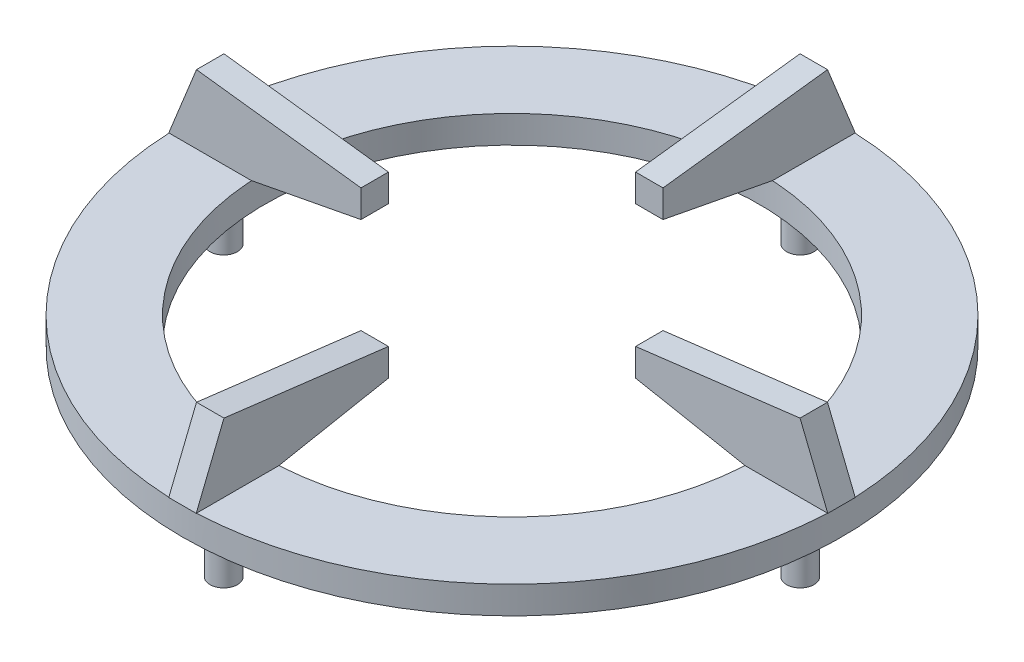
SolidWorks part; units mm, degrees
material "AISI 1010 Steel, hot rolled bar"
ref_plane "Front Plane" through (0, 0, 0) normal (0, 0, 1) x (1, 0, 0)
ref_plane "Top Plane" through (0, 0, 0) normal (0, 1, 0) x (1, 0, 0)
ref_plane "Right Plane" through (0, 0, 0) normal (1, 0, 0) x (0, 0, -1)
sketch "Sketch1" plane through (0, 0, 0) normal (0, 1, 0) x (1, 0, 0)
  circle A0 centre (0, 0) radius 18
  circle A1 centre (0, 0) radius 24
  dimension "D1" = 36
  dimension "D2" = 48
extrude "Boss-Extrude1" add sketch "Sketch1" along normal blind 2
sketch "Sketch3" plane through (0, 0, 0) normal (0, 0, 1) x (1, 0, 0)
  line L0 (24, 2) -> (21.9799, 7)
  line L1 (21.9799, 7) -> (10, 5.5291)
  line L2 (10, 5.5291) -> (10, 3.5291)
  line L3 (10, 3.5291) -> (18, 2)
  line L4 (0, 12.8691) -> (0, -11.8083) construction
  line L5 (24, 2) -> (-24, 2) construction
  line L6 (18, 2) -> (24, 2)
  line L7 (-10, 3.5291) -> (-18, 2)
  line L8 (-10, 5.5291) -> (-10, 3.5291)
  line L9 (-21.9799, 7) -> (-10, 5.5291)
  line L10 (-24, 2) -> (-21.9799, 7)
  line L11 (-18, 2) -> (-24, 2)
  dimension "D1" = 5
  dimension "D2" = 68
  dimension "D3" = 8
  dimension "D4" = 2
  dimension "D5" = 105
extrude "Boss-Extrude2" add sketch "Sketch3" along normal blind 1 and the other way blind 1
sketch "Sketch4" plane through (0, 0, 0) normal (1, 0, 0) x (0, 0, -1)
  line L0 (24, 2) -> (21.9799, 7)
  line L1 (21.9799, 7) -> (10, 5.5291)
  line L2 (10, 5.5291) -> (10, 3.5291)
  line L3 (10, 3.5291) -> (18, 2)
  line L4 (24, 2) -> (1, 2) construction
  line L5 (0, -8.6387) -> (0, 12.4069) construction
  line L6 (18, 2) -> (24, 2)
  line L7 (-10, 3.5291) -> (-18, 2)
  line L8 (-10, 5.5291) -> (-10, 3.5291)
  line L9 (-21.9799, 7) -> (-10, 5.5291)
  line L10 (-24, 2) -> (-21.9799, 7)
  line L11 (-18, 2) -> (-24, 2)
  dimension "D1" = 5
  dimension "D2" = 8
  dimension "D3" = 2
  dimension "D4" = 68
  dimension "D5" = 105
extrude "Boss-Extrude3" add sketch "Sketch4" along normal blind 1 and the other way blind 1
sketch "Sketch5" plane through (0, 0, 0) normal (0, -1, 0) x (1, 0, 0)
  circle A0 centre (0, 0) radius 21
  circle A1 centre (21, 0) radius 1
  circle A2 centre (0, 21) radius 1
  circle A3 centre (-21, 0) radius 1
  circle A4 centre (0, -21) radius 1
  circle A5 centre (0, 0) radius 24 construction
  dimension "D1" = 42
  dimension "D2" = 2
  dimension "D3" = 21
  dimension "D4" = 21
extrude "Boss-Extrude4" add sketch "Sketch5" along normal blind 4 contours A0 A2 | A0 A2 | A0 A1 | A0 A1 | A0 A3 | A0 A4 | A0 A4 | A3 region at (20.5713, 0, 0) region at (21.4201, 0, 0) region at (0, 0, 20.5713) region at (0, 0, 21.4201) region at (0, 0, -21.4201) region at (0, 0, -20.5713) region at (-21.4201, 0, 0)
